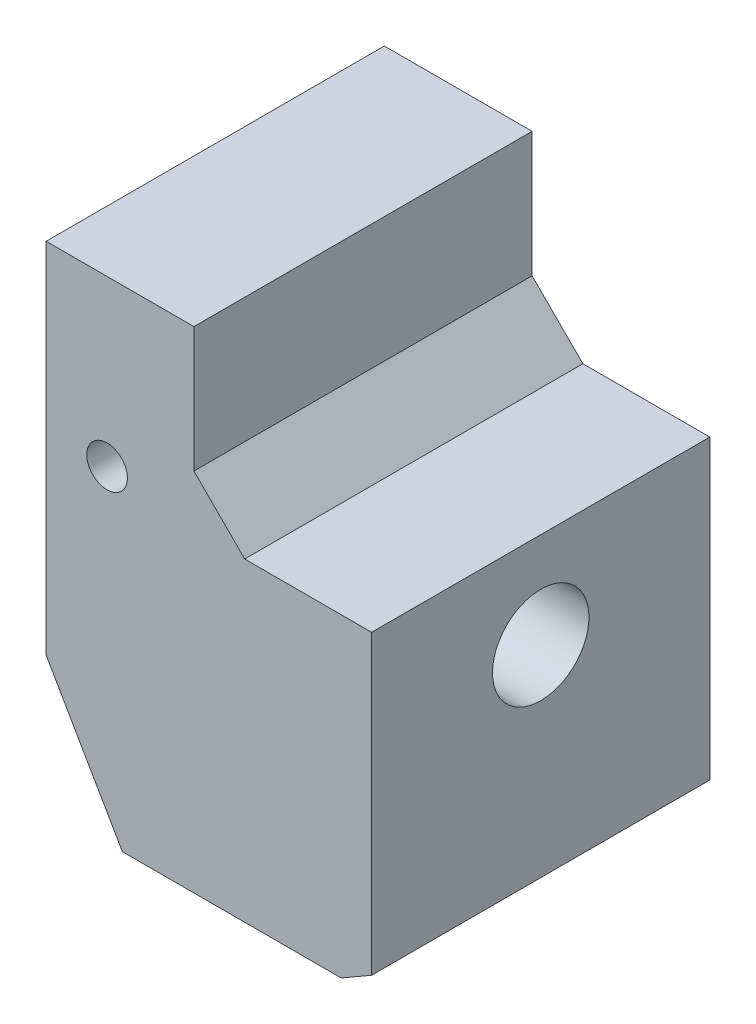
SolidWorks part; units mm, degrees
ref_plane "Front Plane" through (0, 0, 0) normal (0, 0, 1) x (1, 0, 0)
ref_plane "Top Plane" through (0, 0, 0) normal (0, 1, 0) x (1, 0, 0)
ref_plane "Right Plane" through (0, 0, 0) normal (1, 0, 0) x (0, 0, -1)
sketch "Sketch1" plane through (0, 0, 0) normal (1, 0, 0) x (0, 0, -1)
  line L1 (-16.65, 24.15) -> (16.65, 24.15)
  line L2 (-16.65, 24.15) -> (-16.65, -24.15)
  line L3 (-16.65, -24.15) -> (16.65, -24.15)
  line L4 (16.65, 24.15) -> (16.65, -24.15)
  line L5 (-16.65, 24.15) -> (16.65, -24.15) construction
  line L6 (-16.65, -24.15) -> (16.65, 24.15) construction
  point P0 (0, 0)
  dimension "D1" = 48.3
  dimension "D2" = 33.3
extrude "Boss-Extrude1" add sketch "Sketch1" along normal blind 9.55
sketch "Sketch2" plane through (0, 0, 0) normal (-1, 0, 0) x (0, 0, 1)
  line L0 (0, 24.15) -> (0, 19.15) construction
  line L1 (-4.5, 12.6332) -> (-4.5, 19.15)
  line L2 (-4.5, 12.6332) -> (-5.65, 11.45)
  line L3 (-16.65, 24.15) -> (16.65, 24.15) construction
  line L4 (0, 19.15) -> (0, -19.451) construction
  line L5 (0, -19.451) -> (0, -24.15) construction
  line L6 (16.65, -24.15) -> (-16.65, -24.15) construction
  line L7 (4.5, 19.15) -> (5.65, 19.15)
  line L8 (-11.65, -9.1) -> (-11.65, -0.8374)
  line L9 (-11.65, -9.95) -> (11.65, -9.95)
  line L10 (-5.5, 13.0391) -> (-5.5, 20.15)
  line L11 (4.5, 20.15) -> (-5.5, 20.15)
  line L12 (-11.65, -9.95) -> (-11.65, -9.1)
  line L13 (4.5, 20.15) -> (6.65, 20.15)
  line L14 (11.65, -9.95) -> (11.65, -9.1)
  line L15 (6.65, 20.15) -> (6.65, 5.9938)
  line L16 (6.65, 5.9938) -> (12.65, -0.4436)
  line L17 (12.65, -0.4436) -> (12.65, -9.1)
  line L18 (12.65, -10.95) -> (12.65, -9.1)
  line L19 (4.5, 19.15) -> (-4.5, 19.15)
  line L20 (-5.65, 5.6) -> (-5.65, 11.45)
  line L21 (-5.65, 5.6) -> (-11.65, -0.8374)
  line L22 (-12.65, -10.95) -> (12.65, -10.95)
  line L23 (-12.65, -10.95) -> (-12.65, -9.1)
  line L24 (-12.65, -9.1) -> (-12.65, -0.4436)
  line L25 (11.65, -0.8374) -> (11.65, -9.1)
  line L26 (5.65, 5.6) -> (11.65, -0.8374)
  line L27 (5.65, 19.15) -> (5.65, 5.6)
  line L28 (-6.65, 5.9938) -> (-12.65, -0.4436)
  line L29 (-6.65, 5.9938) -> (-6.65, 11.8559)
  line L30 (-5.5, 13.0391) -> (-6.65, 11.8559)
  point P16 (0, -10.1)
  dimension "D1" = 5
  dimension "D2" = 4.699
  dimension "D3" = 23.3
  dimension "D4" = 15.55
  dimension "D5" = 11.3
  dimension "D6" = 1.65
  dimension "D7" = 8.8
  dimension "D8" = 13.55
  dimension "D9" = 1
  dimension "D11" = 4.5
extrude "Cut-Extrude1" cut sketch "Sketch2" against normal blind 5.5 contours L27 L7 L19 L1 L2 L20 L21 L8 L12 L9 L14 L25 L26 | L10 L30 L29 L28 L24 L23 L22 L18 L17 L16 L15 L13 L11 L7 L27 L26 L25 L14 L9 L12 L8 L21 L20 L2 L1 L19 region at (0, 1.8051, 0.0888) region at (0, 16.5946, -5.0991)
sketch "Sketch3" plane through (5.5, 0, 0) normal (-1, 0, 0) x (0, 0, 1)
  line L0 (5.65, 19.15) -> (-4.5, 19.15)
  line L1 (-5.65, 5.45) -> (5.65, 5.45)
  line L2 (-5.65, 11.45) -> (-4.5, 12.6332)
  line L3 (-4.5, 12.6332) -> (-4.5, 19.15)
  line L4 (-5.65, 11.45) -> (-5.65, 5.45)
  line L5 (6.65, 20.15) -> (-5.5, 20.15)
  line L6 (0, 5.45) -> (0, 19.15) construction
  line L7 (-5.5, 13.0391) -> (-5.5, 20.15)
  line L8 (-6.65, 11.8559) -> (-5.5, 13.0391)
  line L9 (-6.65, 11.8559) -> (-6.65, 4.45)
  line L10 (-6.65, 4.45) -> (6.65, 4.45)
  line L11 (5.65, 5.45) -> (5.65, 19.15)
  line L12 (6.65, 4.45) -> (6.65, 20.15)
  dimension "D1" = 1
extrude "Cut-Extrude2" cut sketch "Sketch3" against normal blind 5 contours L6 L1 L11 L0 | L1 L6 L0 L3 L2 L4 | L10 L12 L5 L7 L8 L9 L11 L1 L4 L2 L3 L0 region at (5.5, 12.3, 2.825) region at (5.5, 11.9118, -2.5574) region at (5.5, 12.3, 6.4442)
sketch "Sketch5" plane through (9.55, 0, 0) normal (1, 0, 0) x (0, 0, -1)
  line L1 (-16.65, 24.15) -> (16.65, 24.15)
  line L2 (-16.65, 24.15) -> (-16.65, -24.15)
  line L3 (-16.65, -24.15) -> (16.65, -24.15)
  line L4 (16.65, 24.15) -> (16.65, -24.15)
  line L5 (-16.65, 24.15) -> (16.65, -24.15) construction
  line L6 (-16.65, -24.15) -> (16.65, 24.15) construction
  point P0 (0, 0)
extrude "Boss-Extrude3" add sketch "Sketch5" along normal blind 22.5
sketch "Sketch6" plane through (5.5, 0, 0) normal (-1, 0, 0) x (0, 0, 1)
  line L0 (0, 5.45) -> (0, -2.575) construction
  line L1 (-5.65, 5.45) -> (5.65, 5.45) construction
  line L2 (0, 1.45) -> (5.4752, 1.45) construction
  circle A0 centre (0, -2.575) radius 4.025
  dimension "D2" = 8.05
  dimension "D1" = 4
extrude "Cut-Extrude3" cut sketch "Sketch6" against normal blind 12
sketch "Sketch7" plane through (17.5, 0, 0) normal (-1, 0, 0) x (0, 0, 1)
  circle A0 centre (0, -2.575) radius 4.75
  dimension "D1" = 9.5
extrude "Cut-Extrude4" cut sketch "Sketch7" against normal up to surface (14.55 mm away) up to face at (32.05, 0, 0)
sketch "Sketch27" plane through (0, 0, 5.65) normal (0, 0, -1) x (-1, 0, 0)
  circle A0 centre (-6, 7.95) radius 2
  dimension "D1" = 4
  dimension "D2" = 6
extrude "Cut-Extrude6" cut sketch "Sketch27" against normal through all both and the other way through all
ref_plane "Plane1" through (18.4698, -31.9906, 0) normal (0.5, -0.866, 0) x (0, 0, -1)
sketch "Sketch28" plane through (0, 0, 0) normal (0, 0, 1) x (1, 0, 0)
  line L0 (32.05, -2.575) -> (17.5, -2.575) construction
  line L1 (32.05, -7.325) -> (32.05, 2.175) construction
  line L2 (17.5, -6.6) -> (17.5, 1.45) construction
  line L3 (17.5, -2.575) -> (17.5, -6.6) construction
  line L4 (17.5, -7.325) -> (17.5, 2.175) construction
  line L5 (17.5, -6.6) -> (13.5, -6.6) construction
  line L6 (13.5, -6.6) -> (25.7369, -27.7949)
  line L7 (6.7789, -38.7403) -> (30.1606, -25.2408) construction
  line L8 (13.5, -6.6) -> (11.25, -2.7029)
  dimension "D1" = 4.025
  dimension "D2" = 4
  dimension "D3" = 60
  dimension "D4" = 180
  dimension "D5" = 4.5
sketch "Sketch29" plane through (0, 0, 0) normal (0, 0, 1) x (1, 0, 0)
  line L0 (32.05, -2.575) -> (17.5, -2.575) construction
  line L1 (32.05, -7.325) -> (32.05, 2.175) construction
  line L2 (19.5, -16.9923) -> (25.7369, -27.7949)
  line L3 (17.5, -2.575) -> (17.5, -6.6) construction
  line L4 (6.7789, -38.7403) -> (30.1606, -25.2408) construction
  line L5 (17.5, -6.6) -> (13.5, -6.6) construction
  line L6 (13.5, -6.6) -> (19.5, -16.9923) construction
  line L8 (13.5, -6.6) -> (25.7369, -27.7949) construction
  dimension "D1" = 4.025
  dimension "D2" = 4
  dimension "D3" = 12
  dimension "D4" = 60
sketch "Sketch30" plane through (18.4698, -31.9906, 0) normal (0.5, -0.866, 0) x (0, 0, -1)
  circle A0 centre (0, 8.3913) radius 4
  dimension "D1" = 8
sweep "Cut-Sweep1" cut profiles "Sketch30" path "Sketch28"
sketch "Sketch31" plane through (18.4698, -31.9906, 0) normal (0.5, -0.866, 0) x (0, 0, -1)
  circle A0 centre (0, 8.3913) radius 5
  dimension "D1" = 10
sweep "Cut-Sweep2" cut profiles "Sketch31" path "Sketch29"
chamfer "Chamfer1" distance 13 angle 30 1 edges at (0, -24.15, 0) first distance on face at (0, 0, 0)
chamfer "Chamfer2" distance 10 angle 60 1 edges at (32.05, 24.15, 0) first distance on face at (16.025, 24.15, 0)
chamfer "Chamfer3" distance 3 angle 30 1 edges at (32.05, -24.15, 0) first distance on face at (29.406, -24.15, 0)
sketch "Croquis2" plane through (0, 0, 16.65) normal (0, 0, 1) x (1, 0, 0)
  line L0 (32.05, 6.8295) -> (14.55, 6.8295)
  line L1 (14.55, 6.8295) -> (14.55, 24.15)
  line L2 (22.05, 24.15) -> (0, 24.15) construction
  line L3 (14.55, 24.15) -> (32.05, 24.15)
  line L4 (32.05, 24.15) -> (32.05, 6.8295)
  dimension "D1" = 17.5
  dimension "D2" = 17.5
extrude "Cortar-Extruir1" cut sketch "Croquis2" against normal blind 48
chamfer "Chamfer4" distance 5 angle 45 1 edges at (14.55, 6.8295, 0)
sketch "Sketch33" plane through (0, 0, 0) normal (-1, 0, 0) x (0, 0, 1)
  line L0 (0, -9.95) -> (0, -15.45)
  line L1 (-11.65, -9.95) -> (11.65, -9.95) construction
  line L2 (0, -15.45) -> (2.5, -15.45)
  line L3 (2.5, -15.45) -> (2.5, -9.95)
  line L4 (-11.65, -9.95) -> (11.65, -9.95) construction
  line L5 (2.5, -9.95) -> (0, -9.95)
  dimension "D1" = 5.5
  dimension "D2" = 2.5
sketch "Sketch34" plane through (5.5, 0, 0) normal (-1, 0, 0) x (0, 0, 1)
  line L0 (0, -9.95) -> (2.5, -9.95)
  line L1 (-11.65, -9.95) -> (11.65, -9.95) construction
  line L2 (2.5, -9.95) -> (2.5, -10.45)
  line L3 (2.5, -10.45) -> (0, -10.45)
  line L4 (0, -10.45) -> (0, -9.95)
  dimension "D1" = 0.5
loft "Cut-Loft2" cut profiles "Sketch33", "Sketch34" connector at (0, -15.45, 2.5) connector at (5.5, -10.45, 2.5)
